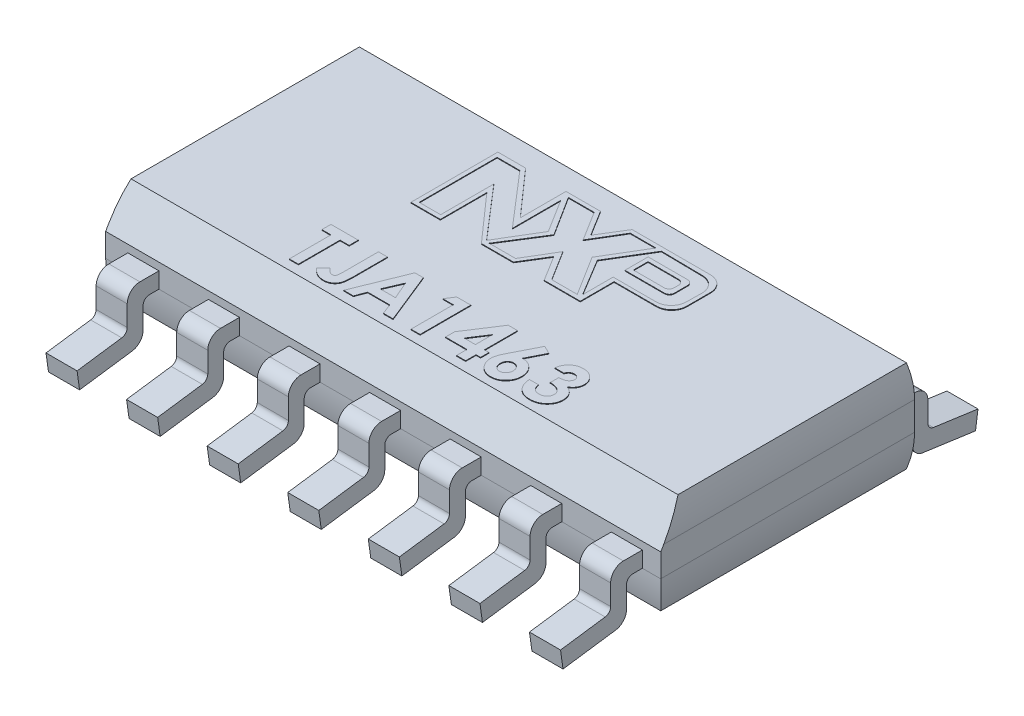
SolidWorks part; units mm, degrees
ref_plane "Front Plane" through (0, 0, 0) normal (0, 0, 1) x (1, 0, 0)
ref_plane "Top Plane" through (0, 0, 0) normal (0, 1, 0) x (1, 0, 0)
ref_plane "Right Plane" through (0, 0, 0) normal (1, 0, 0) x (0, 0, -1)
sketch "Sketch1" plane through (0, 0, 0) normal (0, 1, 0) x (1, 0, 0)
  line L1 (-4.375, 2) -> (4.375, 2)
  line L2 (-4.375, 2) -> (-4.375, -2)
  line L3 (-4.375, -2) -> (4.375, -2)
  line L4 (4.375, 2) -> (4.375, -2)
  line L5 (-4.375, 2) -> (4.375, -2) construction
  line L6 (-4.375, -2) -> (4.375, 2) construction
  point P0 (0, 0)
  dimension "D1" = 8.75
  dimension "D2" = 4
extrude "Boss-Extrude1" add sketch "Sketch1" along normal blind 1.45
sketch "Sketch2" plane through (-4.375, 0, 0) normal (-1, 0, 0) x (0, 0, 1)
  line L0 (2, 0.8687) -> (1.6644, 1.45)
  line L1 (2, 1.45) -> (2, 0) construction
  line L2 (-2, 1.45) -> (2, 1.45) construction
  line L3 (0, 0) -> (0, 0.828) construction
  line L4 (-2, 0.725) -> (-1.3983, 0.725) construction
  line L6 (-2, 1.45) -> (-2, 0) construction
  line L7 (-1.8644, 1.6722) -> (-2.1559, 1.6722)
  line L8 (-2.1559, 1.6722) -> (-2.1559, 0.954)
  line L9 (-2.1559, 0.954) -> (-2, 0.9484)
  line L10 (-2, 0.5016) -> (-2.1559, 0.5016)
  line L11 (-2.1559, 0.5016) -> (-2.1559, -0.2223)
  line L12 (-2.1559, -0.2223) -> (-1.8644, -0.2222)
  line L13 (1.6644, 1.45) -> (1.6644, 1.7317)
  line L14 (1.6644, 1.7317) -> (2.4871, 1.7317)
  line L15 (2.4871, 1.7317) -> (2.4871, 0.8687)
  line L16 (2.4871, 0.8687) -> (2, 0.8687)
  line L17 (2, 0.5015) -> (2.4871, 0.5015)
  line L18 (2.4871, 0.5015) -> (2.4871, -0.2223)
  line L19 (2.4871, -0.2223) -> (1.8644, -0.2223)
  arc A0 (2, 0.5015) -> (1.8644, -0.2223) centre (0, 0.5016) cw
  arc A1 (-2, 0.5016) -> (-1.8644, -0.2222) centre (0, 0.5016) ccw
  arc A2 (-2, 0.9484) -> (-1.8644, 1.6722) centre (0, 0.9484) cw
  dimension "D1" = 2
  dimension "D2" = 60
extrude "Cut-Extrude1" cut sketch "Sketch2" against normal blind 61.45
sketch "Sketch5" plane through (0, 0, -2) normal (0, 0, -1) x (-1, 0, 0)
  line L1 (0, 1.45) -> (0, 1.0867) construction
  line L2 (-5.1778, 0.725) -> (-4.5761, 0.725) construction
  line L3 (-4.2394, 1.6723) -> (-4.5309, 1.6723)
  line L4 (-4.5309, 1.6723) -> (-4.5309, 0.954)
  line L5 (-4.5309, 0.954) -> (-4.375, 0.9484)
  line L6 (-4.375, 0.5016) -> (-4.5309, 0.5016)
  line L7 (-4.5309, 0.5016) -> (-4.5309, -0.2223)
  line L8 (-4.5309, -0.2223) -> (-4.2394, -0.2223)
  line L16 (4.375, 1.45) -> (-4.375, 1.45) construction
  line L17 (-4.5309, 1.6723) -> (-4.2394, 1.6723)
  line L18 (-4.5309, 0.9484) -> (-4.5309, 1.6723)
  line L19 (-4.375, 0.9484) -> (-4.5309, 0.9484)
  line L20 (-4.5309, 0.496) -> (-4.375, 0.5016)
  line L21 (-4.5309, -0.2223) -> (-4.5309, 0.496)
  line L22 (-4.2394, -0.2223) -> (-4.5309, -0.2223)
  line L23 (4.5309, -0.2223) -> (4.2394, -0.2223)
  line L24 (4.5309, 0.5016) -> (4.5309, -0.2223)
  line L25 (4.375, 0.5016) -> (4.5309, 0.5016)
  line L26 (4.5309, 0.954) -> (4.375, 0.9484)
  line L27 (4.5309, 1.6723) -> (4.5309, 0.954)
  line L28 (4.2394, 1.6723) -> (4.5309, 1.6723)
  arc A1 (-4.375, 0.5016) -> (-4.2394, -0.2223) centre (-2.375, 0.5015) ccw
  arc A2 (-4.375, 0.9484) -> (-4.2394, 1.6723) centre (-2.375, 0.9485) cw
  arc A3 (-4.375, 0.5016) -> (-4.2394, -0.2223) centre (-2.375, 0.5015) ccw
  arc A4 (-4.375, 0.9484) -> (-4.2394, 1.6723) centre (-2.375, 0.9485) cw
  arc A5 (4.375, 0.5016) -> (4.2394, -0.2223) centre (2.375, 0.5015) cw
  arc A6 (4.375, 0.9484) -> (4.2394, 1.6723) centre (2.375, 0.9485) ccw
extrude "Cut-Extrude2" cut sketch "Sketch5" against normal blind 61.45 contours L5 A2 L3 L4 | A1 L20 L7 L22 | A6 L26 L27 L28 | L25 A5 L23 L24 region at (4.4265, 1.352, -2) region at (4.4265, 0.0979, -2) region at (-4.4266, 0.0992, -2) region at (-4.4265, 1.352, -2)
sketch "Sketch6" plane through (-4.375, 0, 0) normal (-1, 0, 0) x (0, 0, 1)
  line L5 (1.9361, 0) -> (-1.9361, 0) construction
  line L7 (0, 0) -> (0, -0.7239) construction
  line L8 (2.2535, 0.75) -> (2.3, 0.75)
  line L9 (2.5, 0.55) -> (2.5, 0.2276)
  line L10 (2.5, 0.1406) -> (3.25, 0.1406) construction
  line L11 (3.25, 0.1406) -> (3.25, -0.1094) construction
  line L12 (3.25, -0.1094) -> (2.25, -0.1094) construction
  line L13 (2.25, 0.0645) -> (2.25, 0.4)
  line L14 (2.25, 0.5) -> (2.2535, 0.5)
  line L15 (-3.25, -0.1094) -> (-2.25, -0.1094) construction
  line L17 (2.4222, -0.1335) -> (3.2508, -0.25)
  line L18 (2.5861, 0.1286) -> (3.2901, 0.0296)
  line L19 (3.2508, -0.25) -> (3.2901, 0.0296)
  line L20 (-3.25, 0.1406) -> (-3.25, -0.1094) construction
  line L21 (-2.5, 0.1406) -> (-3.25, 0.1406) construction
  line L22 (-3.2508, -0.25) -> (-3.2901, 0.0296)
  line L23 (-2.5861, 0.1286) -> (-3.2901, 0.0296)
  line L24 (-2.4222, -0.1335) -> (-3.2508, -0.25)
  line L25 (-2.25, 0.5) -> (-2.2535, 0.5)
  line L26 (-2.25, 0.0645) -> (-2.25, 0.4)
  line L27 (-2.5, 0.55) -> (-2.5, 0.2276)
  line L28 (-2.2535, 0.75) -> (-2.3, 0.75)
  line L29 (-2.15, 0.5) -> (2.15, 0.5)
  line L30 (-2.2535, 0.75) -> (2.2535, 0.75)
  arc A0 (2.4222, -0.1335) -> (2.25, 0.0645) centre (2.45, 0.0645) cw
  arc A1 (2.5, 0.55) -> (2.3, 0.75) centre (2.3, 0.55) ccw
  arc A2 (2.5861, 0.1286) -> (2.5, 0.2276) centre (2.6, 0.2276) cw
  arc A3 (2.25, 0.4) -> (2.15, 0.5) centre (2.15, 0.4) ccw
  arc A4 (-2.25, 0.4) -> (-2.15, 0.5) centre (-2.15, 0.4) cw
  arc A5 (-2.5861, 0.1286) -> (-2.5, 0.2276) centre (-2.6, 0.2276) ccw
  arc A6 (-2.5, 0.55) -> (-2.3, 0.75) centre (-2.3, 0.55) cw
  arc A7 (-2.4222, -0.1335) -> (-2.25, 0.0645) centre (-2.45, 0.0645) ccw
  line M15 (-2, 0.9484) -> (-2, 0.5016)
  line M17 (2, 0.5016) -> (2, 0.8687)
  dimension "D9" = 0.2
  dimension "D10" = 0.1
  dimension "D4" = 0.25
  dimension "D5" = 0.25
  dimension "D6" = 1
  dimension "D7" = 8
  dimension "D8" = 0.25
extrude "Boss-Extrude2" add sketch "Sketch6" against normal up to surface (8.75 mm away) contours L30 M15 M17 | L24 A7 L26 A4 L29 A3 L13 A0 L17 L19 L18 A2 L9 A1 L8 L30 L28 A6 L27 A5 L23 L22 region at (-4.375, 0.6834, 2.2768) up to face at (4.375, 0.8431, 0.3908)
sketch "Sketch7" plane through (0, 1.45, 0) normal (0, 1, 0) x (1, 0, 0)
  line L0 (4.375, -2) -> (-4.375, -2) construction
  line L1 (-4.375, -2) -> (-4.025, -2)
  line L2 (-4.375, -2) -> (-4.375, -3.534)
  line L3 (-4.375, -3.534) -> (-4.025, -3.534)
  line L4 (-4.025, -2) -> (-4.025, -3.534)
  line L5 (-3.535, -2) -> (-2.755, -2)
  line L6 (-3.535, -2) -> (-3.535, -3.6106)
  line L7 (-3.535, -3.6106) -> (-2.755, -3.6106)
  line L8 (-2.755, -2) -> (-2.755, -3.6106)
  line L9 (0, 0) -> (-3.4858, 0) construction
  line L10 (-2.265, -2) -> (-1.485, -2)
  line L11 (-2.265, -2) -> (-2.265, -3.6106)
  line L12 (-2.265, -3.6106) -> (-1.485, -3.6106)
  line L13 (-1.485, -2) -> (-1.485, -3.6106)
  line L14 (1.055, -2) -> (0.275, -2)
  line L15 (1.055, -2) -> (1.055, -3.783)
  line L16 (1.055, -3.783) -> (0.275, -3.783)
  line L17 (0.275, -2) -> (0.275, -3.783)
  line L18 (-0.215, -2) -> (-0.995, -2)
  line L19 (-0.215, -2) -> (-0.215, -3.6776)
  line L20 (-0.215, -3.6776) -> (-0.995, -3.6776)
  line L21 (-0.995, -2) -> (-0.995, -3.6776)
  line L22 (-0.995, 2) -> (-0.995, 3.6776)
  line L23 (-0.215, 3.6776) -> (-0.995, 3.6776)
  line L24 (-0.215, 2) -> (-0.215, 3.6776)
  line L25 (-0.215, 2) -> (-0.995, 2)
  line L26 (0.275, 2) -> (0.275, 3.783)
  line L27 (1.055, 3.783) -> (0.275, 3.783)
  line L28 (1.055, 2) -> (1.055, 3.783)
  line L29 (1.055, 2) -> (0.275, 2)
  line L30 (-1.485, 2) -> (-1.485, 3.6106)
  line L31 (-2.265, 3.6106) -> (-1.485, 3.6106)
  line L32 (-2.265, 2) -> (-2.265, 3.6106)
  line L33 (-2.265, 2) -> (-1.485, 2)
  line L34 (-2.755, 2) -> (-2.755, 3.6106)
  line L35 (-3.535, 3.6106) -> (-2.755, 3.6106)
  line L36 (-3.535, 2) -> (-3.535, 3.6106)
  line L37 (-3.535, 2) -> (-2.755, 2)
  line L38 (-4.025, 2) -> (-4.025, 3.534)
  line L39 (-4.375, 3.534) -> (-4.025, 3.534)
  line L40 (-4.375, 2) -> (-4.375, 3.534)
  line L41 (-4.375, 2) -> (-4.025, 2)
  line L42 (4.375, -2) -> (-4.375, -2) construction
  line L43 (1.545, -2) -> (2.325, -2)
  line L44 (1.545, -2) -> (1.545, -3.783)
  line L45 (1.545, -3.783) -> (2.325, -3.783)
  line L46 (2.325, -2) -> (2.325, -3.783)
  line L47 (4.085, 2) -> (4.085, 3.8801)
  line L48 (2.815, -2) -> (3.595, -2)
  line L49 (2.815, -2) -> (2.815, -4.1331)
  line L50 (2.815, -4.1331) -> (3.595, -4.1331)
  line L51 (3.595, -2) -> (3.595, -4.1331)
  line L52 (4.375, -2) -> (4.085, -2)
  line L53 (4.375, -2) -> (4.375, -3.8801)
  line L54 (4.375, -3.8801) -> (4.085, -3.8801)
  line L55 (4.085, -2) -> (4.085, -3.8801)
  line L56 (4.375, 3.8801) -> (4.085, 3.8801)
  line L57 (4.375, 2) -> (4.375, 3.8801)
  line L58 (4.375, 2) -> (4.085, 2)
  line L59 (3.595, 2) -> (3.595, 4.1331)
  line L60 (2.815, 4.1331) -> (3.595, 4.1331)
  line L61 (2.815, 2) -> (2.815, 4.1331)
  line L62 (2.815, 2) -> (3.595, 2)
  line L63 (2.325, 2) -> (2.325, 3.783)
  line L64 (1.545, 3.783) -> (2.325, 3.783)
  line L65 (1.545, 2) -> (1.545, 3.783)
  line L66 (1.545, 2) -> (2.325, 2)
  point P62 (4.085, -2.9401)
  dimension "D1" = 0.49
  dimension "D2" = 0.49
  dimension "D3" = 0.49
  dimension "D4" = 0.49
  dimension "D5" = 0.78
  dimension "D6" = 0.78
  dimension "D7" = 0.78
  dimension "D8" = 0.35
  dimension "D9" = 0.49
  dimension "D10" = 0.49
  dimension "D11" = 0.78
  dimension "D12" = 0.78
  dimension "D13" = 0.78
  dimension "D14" = 0.49
extrude "Cut-Extrude3" cut sketch "Sketch7" against normal blind 61.45 body kept at (4.375, 0.8687, 2)
sketch "Sketch8" plane through (0, 1.45, 0) normal (0, 1, 0) x (1, 0, 0)
  line L0 (70.6653, 255.7964) -> (518.6653, 255.7964) construction
  line L1 (-1.775, 0.2105) -> (-1.775, 1.5827)
  line L2 (-1.775, 1.5827) -> (-1.3388, 1.5827)
  line L3 (-1.3388, 1.5827) -> (-0.7012, 0.8616)
  line L4 (-0.7012, 0.8616) -> (-0.7012, 1.5827)
  line L5 (-0.7012, 1.5827) -> (-0.1577, 1.5827)
  line L6 (-0.1577, 1.5827) -> (0.092, 1.1801)
  line L7 (0.092, 1.1801) -> (0.3406, 1.5827)
  line L8 (0.3406, 1.5827) -> (1.577, 1.5827)
  line L9 (1.817, 1.3427) -> (1.817, 0.9698)
  line L10 (1.577, 0.7298) -> (0.91, 0.7298)
  line L11 (0.91, 0.7298) -> (0.91, 0.1964)
  line L12 (0.91, 0.1964) -> (0.3406, 0.1964)
  line L13 (0.3406, 0.1964) -> (0.092, 0.5973)
  line L14 (0.092, 0.5973) -> (-0.1512, 0.2035)
  line L15 (-0.1512, 0.2035) -> (-0.6559, 0.2035)
  line L16 (-0.6559, 0.2035) -> (-1.3094, 0.9426)
  line L17 (-1.3094, 0.9426) -> (-1.3094, 0.2105)
  line L18 (-1.3094, 0.2105) -> (-1.775, 0.2105)
  line L19 (-1.7094, 0.2766) -> (-1.7094, 1.5045)
  line L20 (-1.7094, 1.5045) -> (-1.3506, 1.5045)
  line L21 (-1.3506, 1.5045) -> (-0.6198, 0.6555)
  line L22 (-0.6198, 0.6555) -> (-0.6198, 1.4187)
  line L23 (-0.6198, 1.4187) -> (-0.2937, 0.8962)
  line L24 (-0.2937, 0.8962) -> (-0.6592, 0.288)
  line L25 (-0.6592, 0.288) -> (-1.3716, 1.1155)
  line L26 (-1.3716, 1.1155) -> (-1.3716, 0.2766)
  line L27 (-1.3716, 0.2766) -> (-1.7094, 0.2766)
  line L28 (-0.5996, 1.5187) -> (-0.1938, 1.5187)
  line L29 (-0.1938, 1.5187) -> (0.0963, 1.0543)
  line L30 (0.0963, 1.0543) -> (0.3747, 1.5187)
  line L31 (0.3747, 1.5187) -> (0.7798, 1.5187)
  line L32 (0.7798, 1.5187) -> (0.4027, 0.8897)
  line L33 (0.4027, 0.8897) -> (0.7926, 0.2655)
  line L34 (0.7926, 0.2655) -> (0.3902, 0.2655)
  line L35 (0.3902, 0.2655) -> (0.0963, 0.736)
  line L36 (0.0963, 0.736) -> (-0.1833, 0.2695)
  line L37 (-0.1833, 0.2695) -> (-0.5996, 0.2695)
  line L38 (-0.5996, 0.2695) -> (-0.205, 0.8962)
  line L39 (-0.205, 0.8962) -> (-0.5996, 1.5187)
  line L40 (0.8664, 1.5187) -> (1.5222, 1.5095)
  line L41 (1.7588, 1.2662) -> (1.7554, 1.0214)
  line L42 (1.5154, 0.7847) -> (0.8395, 0.7847)
  line L43 (0.8395, 0.7847) -> (0.8395, 0.3024)
  line L44 (0.8395, 0.3024) -> (0.4854, 0.8897)
  line L45 (0.4854, 0.8897) -> (0.8664, 1.5187)
  line L46 (0.8395, 1.3362) -> (1.4613, 1.3362)
  line L47 (1.5413, 1.2562) -> (1.5413, 1.0498)
  line L48 (1.4613, 0.9698) -> (0.8395, 0.9698)
  line L49 (0.8395, 1.3362) -> (0.8395, 0.9698)
  line L50 (0.9038, 1.2698) -> (1.3866, 1.2698)
  line L51 (0.9038, 1.2698) -> (0.9038, 1.0405)
  line L52 (0.9038, 1.0405) -> (1.3866, 1.0405)
  line L53 (1.4666, 1.1898) -> (1.4666, 1.1205)
  arc A0 (1.817, 0.9698) -> (1.577, 0.7298) centre (1.577, 0.9698) cw
  arc A1 (1.577, 1.5827) -> (1.817, 1.3427) centre (1.577, 1.3427) cw
  arc A2 (1.7554, 1.0214) -> (1.5154, 0.7847) centre (1.5154, 1.0247) cw
  arc A3 (1.5222, 1.5095) -> (1.7588, 1.2662) centre (1.5188, 1.2695) cw
  arc A4 (1.3866, 1.0405) -> (1.4666, 1.1205) centre (1.3866, 1.1205) ccw
  arc A5 (1.3866, 1.2698) -> (1.4666, 1.1898) centre (1.3866, 1.1898) cw
  arc A6 (1.5413, 1.0498) -> (1.4613, 0.9698) centre (1.4613, 1.0498) cw
  arc A7 (1.4613, 1.3362) -> (1.5413, 1.2562) centre (1.4613, 1.2562) cw
extrude "Boss-Extrude3" add sketch "Sketch8" along normal blind 0.01 contours A1 L8 L7 L6 L5 L4 L3 L2 L1 L18 L17 L16 L15 L14 L13 L12 L11 L10 A0 L9 L38 L39 L28 L29 L30 L31 L32 L33 L34 L35 L36 L37 L26 L27 L19 L20 L21 L22 L23 L24 L25 L40 A3 L41 A2 L42 L43 L44 | A7 L46 L49 L48 A6 L47 L50 A5 L53 A4 L52 L51 region at (-1.7365, 1.45, -0.8966) region at (1.1504, 1.45, -1.3282)
sketch "Sketch9" plane through (0, 1.45, 0) normal (0, 1, 0) x (1, 0, 0)
  line L0 (-2.1144, -1.5197) -> (3.2848, -1.5197) construction
  text T0 "<b>TJA1463</b>" font "Century Gothic" height 0.8
extrude "Boss-Extrude4" add sketch "Sketch9" along normal blind 0.01
